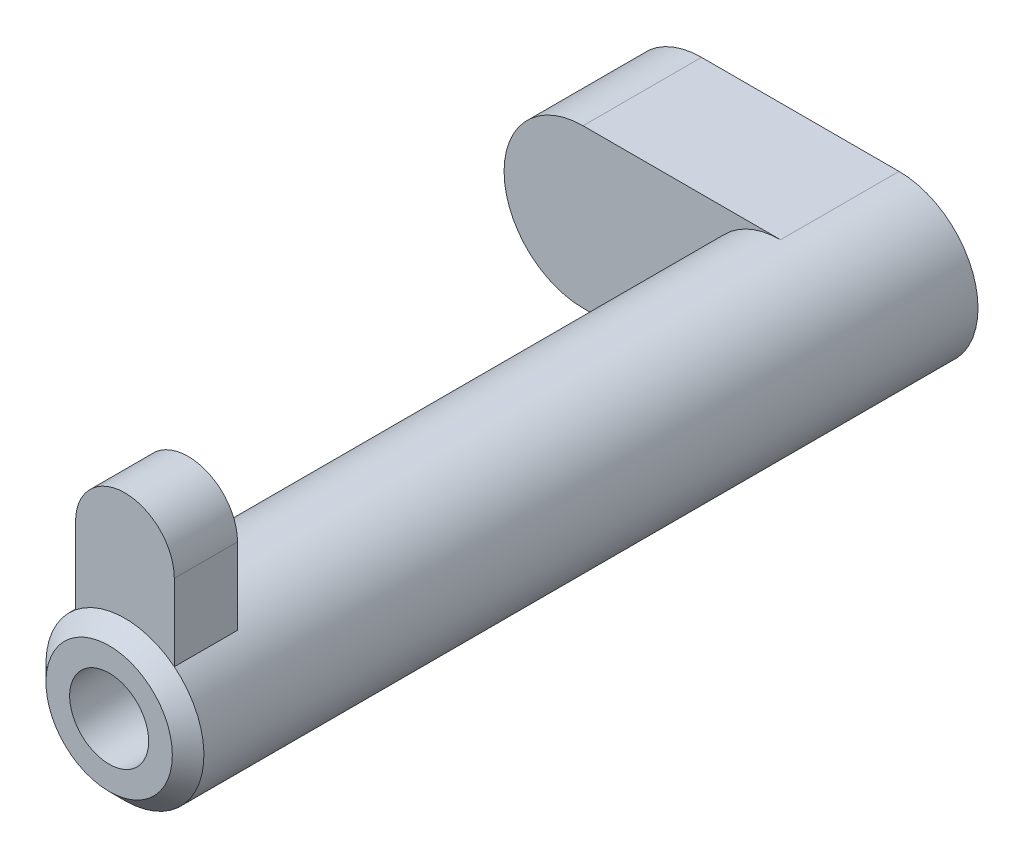
SolidWorks part; units mm, degrees
ref_plane "Ebene vorne" through (0, 0, 0) normal (0, 0, 1) x (1, 0, 0)
ref_plane "Ebene oben" through (0, 0, 0) normal (0, 1, 0) x (1, 0, 0)
ref_plane "Ebene rechts" through (0, 0, 0) normal (1, 0, 0) x (0, 0, -1)
sketch "Skizze1" plane through (0, 0, 0) normal (0, 0, 1) x (1, 0, 0)
  line L0 (0, 2) -> (-5, 2)
  line L1 (-5, -2) -> (0, -2)
  arc A1 (0, 2) -> (0, -2) centre (0, 0) cw
  arc A2 (-5, 2) -> (-5, -2) centre (-5, 0) ccw
  dimension "D1" = 4
  dimension "D2" = 5
extrude "Aufsatz-Linear austragen1" add sketch "Skizze1" along normal blind 3
sketch "Skizze2" plane through (0, 0, 3) normal (0, 0, 1) x (1, 0, 0)
  circle A0 centre (0, 0) radius 2
  arc A1 (0, -2) -> (0, 2) centre (0, 0) ccw construction
  dimension "D1" = 4
extrude "Aufsatz-Linear austragen2" add sketch "Skizze2" along normal blind 17
sketch "Skizze3" plane through (0, 0, 3) normal (0, 0, 1) x (1, 0, 0)
  line L0 (0, 0) -> (0, 3.5) construction
  line L1 (-1.25, 1.5612) -> (-1.25, 3.5)
  line L2 (1.25, 1.5612) -> (1.25, 3.5)
  arc A0 (-1.25, 3.5) -> (1.25, 3.5) centre (0, 3.5) cw
  circle A1 centre (0, 0) radius 2
  circle A2 centre (0, 0) radius 2
  dimension "D2" = 3.5
  dimension "D3" = 2.5
  dimension "D1" = 0
extrude "Aufsatz-Linear austragen3" add sketch "Skizze3" along normal blind 1.6 from offset 15
sketch "Skizze4" plane through (0, 0, 20) normal (0, 0, 1) x (1, 0, 0)
  circle A1 centre (0, 0) radius 1
  dimension "D1" = 2
extrude "Schnitt-Linear austragen1" cut sketch "Skizze4" against normal up to next
chamfer "Fase1" distance 0.4 angle 45 1 edges at (2, 0, 20)
